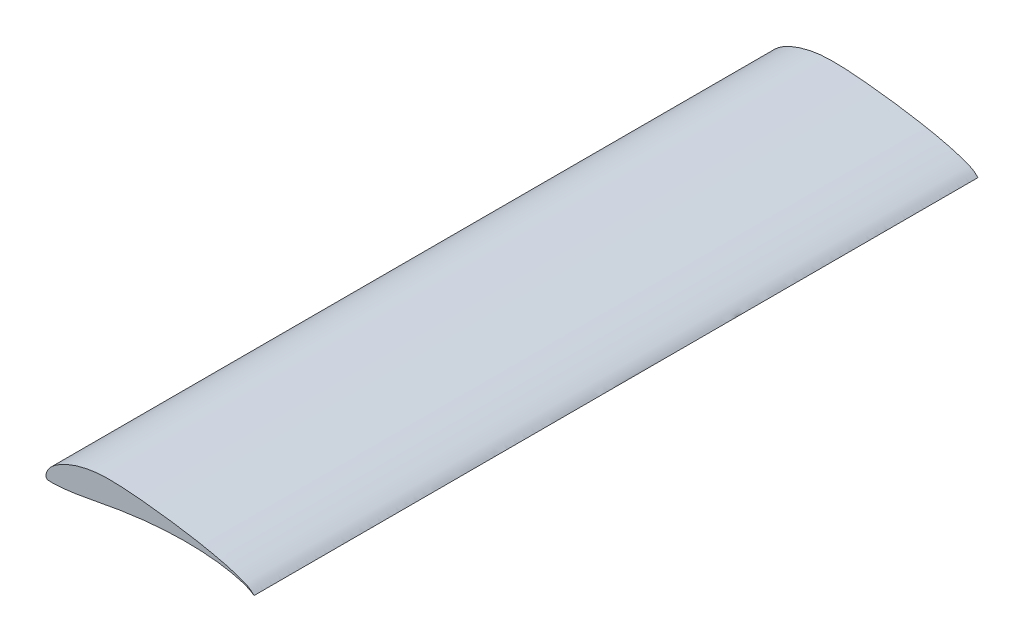
SolidWorks part; units mm, degrees
ref_plane "Front Plane" through (0, 0, 0) normal (0, 0, 1) x (1, 0, 0)
ref_plane "Top Plane" through (0, 0, 0) normal (0, 1, 0) x (1, 0, 0)
ref_plane "Right Plane" through (0, 0, 0) normal (1, 0, 0) x (0, 0, -1)
curve "Curve1"
  spline degree 3 poles (290.9696, 0.7585, 0) (292.3648, -0.1886, 0) (291.1415, 0.7229, 0) (290.3294, 1.5197, 0) (288.5262, 3.184, 0) (286.3989, 4.9545, 0) (283.4889, 6.7393, 0) (279.8703, 8.469, 0) (275.5017, 10.2742, 0) (270.39, 12.1297, 0) (264.5588, 14.0224, 0) (258.0385, 15.9359, 0) (250.8656, 17.8611, 0) (243.0797, 19.7805, 0) (234.7254, 21.6801, 0) (225.8525, 23.5481, 0) (216.5152, 25.3748, 0) (206.7681, 27.1378, 0) (196.6726, 28.8346, 0) (186.2868, 30.4432, 0) (175.6779, 31.9669, 0) (164.9139, 33.3936, 0) (154.0728, 34.7187, 0) (143.2411, 35.9516, 0) (132.5087, 37.0612, 0) (121.9629, 38.0267, 0) (111.6779, 38.7938, 0) (101.7125, 39.3214, 0) (92.122, 39.5493, 0) (82.9557, 39.525, 0) (74.2306, 39.0762, 0) (65.9433, 38.1667, 0) (58.0601, 36.8807, 0) (50.5792, 35.2146, 0) (43.5081, 33.2609, 0) (36.8768, 31.0542, 0) (30.7135, 28.6461, 0) (25.0566, 26.0495, 0) (19.9241, 23.317, 0) (15.344, 20.4799, 0) (11.3449, 17.5764, 0) (7.9286, 14.6682, 0) (5.1446, 11.7236, 0) (3.0062, 8.7679, 0) (1.4265, 5.8925, 0) (0.4142, 3.1624, 0) (-0.0682, 0.6425, 0) (0.0249, -1.4887, 0) (0.5736, -3.4434, 0) (2.6131, -4.4137, 0) (5.3554, -4.5499, 0) (9.1068, -4.6818, 0) (13.8244, -4.4784, 0) (19.4549, -4.1045, 0) (25.9357, -3.5057, 0) (33.2005, -2.6955, 0) (41.2137, -1.6564, 0) (49.9716, -0.2042, 0) (59.5167, 1.6168, 0) (69.8968, 3.5987, 0) (81.0611, 5.6913, 0) (92.9395, 7.8077, 0) (105.4448, 9.8685, 0) (118.48, 11.8049, 0) (131.9326, 13.5459, 0) (145.6818, 15.0408, 0) (159.5977, 16.2225, 0) (173.5406, 17.0601, 0) (187.3648, 17.5206, 0) (200.9204, 17.5788, 0) (214.0561, 17.2306, 0) (226.6216, 16.4844, 0) (238.4657, 15.3496, 0) (249.4474, 13.8699, 0) (259.4238, 12.0882, 0) (268.2778, 10.0642, 0) (275.8463, 7.8983, 0) (282.0404, 5.5868, 0) (286.4597, 3.4714, 0) (289.718, 1.5155, 0) (290.9696, 0.7585, 0) (292.3648, -0.1886, 0) (291.1415, 0.7229, 0) knots -0.009748 -0.004147 -0.001 0 0.00098 0.003649 0.007483 0.012095 0.017526 0.024052 0.031783 0.040678 0.05071 0.061833 0.073989 0.087118 0.101145 0.115991 0.13157 0.147788 0.164551 0.181758 0.199312 0.217095 0.23499 0.252857 0.270541 0.287887 0.304773 0.321101 0.336806 0.3518 0.366031 0.379616 0.392653 0.40517 0.417172 0.428604 0.439419 0.449597 0.459102 0.467908 0.475988 0.483309 0.489875 0.495803 0.501149 0.505903 0.510047 0.513579 0.516447 0.51935 0.523823 0.529974 0.537716 0.546968 0.557637 0.56962 0.582804 0.597247 0.613135 0.630444 0.649056 0.668822 0.689595 0.71119 0.733427 0.756094 0.778989 0.80189 0.824567 0.846792 0.868338 0.888978 0.908492 0.926659 0.943286 0.958169 0.971136 0.981956 0.990252 0.995853 0.999 1 1.00098 1.003649 1.007483 periodic
sketch "Sketch2" plane through (0, 0, 0) normal (0, 0, 1) x (1, 0, 0)
  spline S0 degree 3 poles (290.9696, 0.7585) (292.3648, -0.1886) (291.1415, 0.7229) (290.3294, 1.5197) (288.5262, 3.184) (286.3989, 4.9545) (283.4889, 6.7393) (279.8703, 8.469) (275.5017, 10.2742) (270.39, 12.1297) (264.5588, 14.0224) (258.0385, 15.9359) (250.8656, 17.8611) (243.0797, 19.7805) (234.7254, 21.6801) (225.8525, 23.5481) (216.5152, 25.3748) (206.7681, 27.1378) (196.6726, 28.8346) (186.2868, 30.4432) (175.6779, 31.9669) (164.9139, 33.3936) (154.0728, 34.7187) (143.2411, 35.9516) (132.5087, 37.0612) (121.9629, 38.0267) (111.6779, 38.7938) (101.7125, 39.3214) (92.122, 39.5493) (82.9557, 39.525) (74.2306, 39.0762) (65.9433, 38.1667) (58.0601, 36.8807) (50.5792, 35.2146) (43.5081, 33.2609) (36.8768, 31.0542) (30.7135, 28.6461) (25.0566, 26.0495) (19.9241, 23.317) (15.344, 20.4799) (11.3449, 17.5764) (7.9286, 14.6682) (5.1446, 11.7236) (3.0062, 8.7679) (1.4265, 5.8925) (0.4142, 3.1624) (-0.0682, 0.6425) (0.0249, -1.4887) (0.5736, -3.4434) (2.6131, -4.4137) (5.3554, -4.5499) (9.1068, -4.6818) (13.8244, -4.4784) (19.4549, -4.1045) (25.9357, -3.5057) (33.2005, -2.6955) (41.2137, -1.6564) (49.9716, -0.2042) (59.5167, 1.6168) (69.8968, 3.5987) (81.0611, 5.6913) (92.9395, 7.8077) (105.4448, 9.8685) (118.48, 11.8049) (131.9326, 13.5459) (145.6818, 15.0408) (159.5977, 16.2225) (173.5406, 17.0601) (187.3648, 17.5206) (200.9204, 17.5788) (214.0561, 17.2306) (226.6216, 16.4844) (238.4657, 15.3496) (249.4474, 13.8699) (259.4238, 12.0882) (268.2778, 10.0642) (275.8463, 7.8983) (282.0404, 5.5868) (286.4597, 3.4714) (289.718, 1.5155) (290.9696, 0.7585) (292.3648, -0.1886) (291.1415, 0.7229) knots -0.009748 -0.004147 -0.001 0 0.00098 0.003649 0.007483 0.012095 0.017526 0.024052 0.031783 0.040678 0.05071 0.061833 0.073989 0.087118 0.101145 0.115991 0.13157 0.147788 0.164551 0.181758 0.199312 0.217095 0.23499 0.252857 0.270541 0.287887 0.304773 0.321101 0.336806 0.3518 0.366031 0.379616 0.392653 0.40517 0.417172 0.428604 0.439419 0.449597 0.459102 0.467908 0.475988 0.483309 0.489875 0.495803 0.501149 0.505903 0.510047 0.513579 0.516447 0.51935 0.523823 0.529974 0.537716 0.546968 0.557637 0.56962 0.582804 0.597247 0.613135 0.630444 0.649056 0.668822 0.689595 0.71119 0.733427 0.756094 0.778989 0.80189 0.824567 0.846792 0.868338 0.888978 0.908492 0.926659 0.943286 0.958169 0.971136 0.981956 0.990252 0.995853 0.999 1 1.00098 1.003649 1.007483 only from (292.1, 0) to (292.1, 0) construction
  spline S1 degree 3 poles (290.9696, 0.7585) (292.3648, -0.1886) (291.1415, 0.7229) (290.3294, 1.5197) (288.5262, 3.184) (286.3989, 4.9545) (283.4889, 6.7393) (279.8703, 8.469) (275.5017, 10.2742) (270.39, 12.1297) (264.5588, 14.0224) (258.0385, 15.9359) (250.8656, 17.8611) (243.0797, 19.7805) (234.7254, 21.6801) (225.8525, 23.5481) (216.5152, 25.3748) (206.7681, 27.1378) (196.6726, 28.8346) (186.2868, 30.4432) (175.6779, 31.9669) (164.9139, 33.3936) (154.0728, 34.7187) (143.2411, 35.9516) (132.5087, 37.0612) (121.9629, 38.0267) (111.6779, 38.7938) (101.7125, 39.3214) (92.122, 39.5493) (82.9557, 39.525) (74.2306, 39.0762) (65.9433, 38.1667) (58.0601, 36.8807) (50.5792, 35.2146) (43.5081, 33.2609) (36.8768, 31.0542) (30.7135, 28.6461) (25.0566, 26.0495) (19.9241, 23.317) (15.344, 20.4799) (11.3449, 17.5764) (7.9286, 14.6682) (5.1446, 11.7236) (3.0062, 8.7679) (1.4265, 5.8925) (0.4142, 3.1624) (-0.0682, 0.6425) (0.0249, -1.4887) (0.5736, -3.4434) (2.6131, -4.4137) (5.3554, -4.5499) (9.1068, -4.6818) (13.8244, -4.4784) (19.4549, -4.1045) (25.9357, -3.5057) (33.2005, -2.6955) (41.2137, -1.6564) (49.9716, -0.2042) (59.5167, 1.6168) (69.8968, 3.5987) (81.0611, 5.6913) (92.9395, 7.8077) (105.4448, 9.8685) (118.48, 11.8049) (131.9326, 13.5459) (145.6818, 15.0408) (159.5977, 16.2225) (173.5406, 17.0601) (187.3648, 17.5206) (200.9204, 17.5788) (214.0561, 17.2306) (226.6216, 16.4844) (238.4657, 15.3496) (249.4474, 13.8699) (259.4238, 12.0882) (268.2778, 10.0642) (275.8463, 7.8983) (282.0404, 5.5868) (286.4597, 3.4714) (289.718, 1.5155) (290.9696, 0.7585) (292.3648, -0.1886) (291.1415, 0.7229) knots -0.009748 -0.004147 -0.001 0 0.00098 0.003649 0.007483 0.012095 0.017526 0.024052 0.031783 0.040678 0.05071 0.061833 0.073989 0.087118 0.101145 0.115991 0.13157 0.147788 0.164551 0.181758 0.199312 0.217095 0.23499 0.252857 0.270541 0.287887 0.304773 0.321101 0.336806 0.3518 0.366031 0.379616 0.392653 0.40517 0.417172 0.428604 0.439419 0.449597 0.459102 0.467908 0.475988 0.483309 0.489875 0.495803 0.501149 0.505903 0.510047 0.513579 0.516447 0.51935 0.523823 0.529974 0.537716 0.546968 0.557637 0.56962 0.582804 0.597247 0.613135 0.630444 0.649056 0.668822 0.689595 0.71119 0.733427 0.756094 0.778989 0.80189 0.824567 0.846792 0.868338 0.888978 0.908492 0.926659 0.943286 0.958169 0.971136 0.981956 0.990252 0.995853 0.999 1 1.00098 1.003649 1.007483 only from (292.1, 0) to (292.1, 0)
extrude "Boss-Extrude1" add sketch "Sketch2" along normal blind 508 and the other way blind 508
